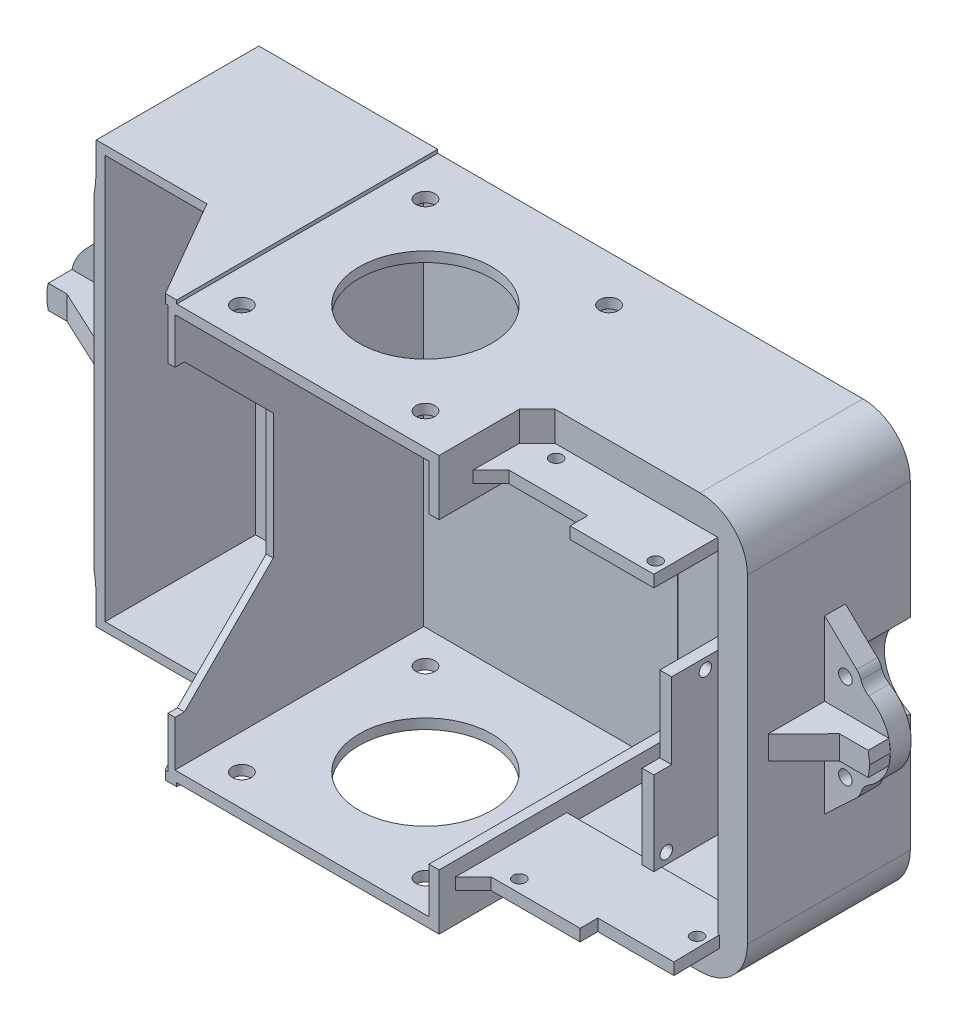
SolidWorks part; units mm, degrees
ref_plane "Front Plane" through (0, 0, 0) normal (0, 0, 1) x (1, 0, 0)
ref_plane "Top Plane" through (0, 0, 0) normal (0, 1, 0) x (1, 0, 0)
ref_plane "Right Plane" through (0, 0, 0) normal (1, 0, 0) x (0, 0, -1)
sketch "Sketch1" plane through (0, 0, 0) normal (0, 0, 1) x (1, 0, 0)
  line L0 (-51.35, -35.6) -> (-51.35, 35.6)
  line L13 (-51.35, 35.6) -> (-21.15, 35.6)
  line L14 (-21.15, -35.6) -> (-21.15, -35)
  line L15 (-51.35, -35.6) -> (-21.15, -35.6)
  line L20 (11, 35) -> (-11, 35) construction
  line L22 (-11, -35) -> (-21.15, -35)
  line L23 (-11, -35) -> (11, -35)
  line L24 (21.15, 33) -> (21.15, 9.5) construction
  line L25 (-21.15, 35) -> (-21.15, 35.6)
  line L29 (23.15, -35) -> (11, -35)
  line L30 (-21.15, 35) -> (23.15, 35)
  line L31 (23.15, 35) -> (23.15, -35)
  line L35 (-21.15, -9.5) -> (-21.15, -33) construction
  line L36 (-23.15, 33.6) -> (-49.35, 33.6) construction
  line L37 (-23.15, -33.6) -> (-49.35, -33.6) construction
  line L38 (-49.35, 33.6) -> (-49.35, -33.6) construction
  point P31 (-23.15, 35)
  dimension "D1" = 2
  dimension "D2" = 2
  dimension "D3" = 2
  dimension "D4" = 2
extrude "Boss-Extrude1" add sketch "Sketch1" along normal up to surface (2.0675 mm away) from offset 2.5
sketch "Sketch2" plane through (0, 0, 4.5675) normal (0, 0, 1) x (1, 0, 0)
  line L0 (-51.35, 35.6) -> (-49.85, 35.6) construction
  line L1 (-21.15, 35.6) -> (-51.35, 35.6) construction
  line L2 (-49.85, 35.6) -> (-49.85, 34.1) construction
  line L3 (-21.15, -35.6) -> (-22.65, -35.6) construction
  line L4 (-51.35, -35.6) -> (-21.15, -35.6) construction
  line L5 (-22.65, -35.6) -> (-22.65, -34.1) construction
  line L7 (-49.85, 34.1) -> (-22.65, 34.1)
  line L8 (-49.85, 34.1) -> (-49.85, -34.1)
  line L9 (-49.85, -34.1) -> (-22.65, -34.1)
  line L10 (-22.65, 34.1) -> (-22.65, -34.1)
  line L11 (-51.35, 35.6) -> (-21.15, 35.6)
  line L12 (-51.35, 35.6) -> (-51.35, -35.6)
  line L13 (-51.35, -35.6) -> (-21.15, -35.6)
  line L14 (-21.15, 35.6) -> (-21.15, -35.6)
  dimension "D1" = 1.5
  dimension "D2" = 1.5
  dimension "D3" = 1.5
  dimension "D4" = 1.5
extrude "Boss-Extrude2" add sketch "Sketch2" along normal blind 25.4
sketch "Sketch3" plane through (0, 0, 4.5675) normal (0, 0, 1) x (1, 0, 0)
  line L0 (-21.15, 33) -> (-21.15, 35)
  line L1 (23.15, -35) -> (-21.15, -35)
  line L2 (23.15, -35) -> (23.15, 35)
  line L3 (23.15, 35) -> (-21.15, 35)
  line L4 (-21.15, -35) -> (-21.15, -33)
  line L5 (21.15, -33) -> (-21.15, -33)
  line L6 (21.15, -33) -> (21.15, 33)
  line L7 (21.15, 33) -> (-21.15, 33)
  line M9 (-21.15, 35) -> (-21.15, -35)
  line M10 (-21.15, -35) -> (23.15, -35)
  line M11 (23.15, -35) -> (23.15, 35)
  line M12 (23.15, 35) -> (-21.15, 35)
extrude "Boss-Extrude3" add sketch "Sketch3" along normal blind 42 contours L7 L6 L5 M9 M10 M11 M12
sketch "Sketch4" plane through (0, 0, 29.9675) normal (0, 0, 1) x (1, 0, 0)
  line L0 (-21.15, 35.6) -> (-51.35, 35.6) construction
  line L1 (-21.15, -35.6) -> (-22.65, -35.6)
  line L2 (-21.15, -35.6) -> (-21.15, -25.6)
  line L3 (-21.15, 35.6) -> (-22.65, 35.6)
  line L5 (-22.65, -35.6) -> (-22.65, -25.6) construction
  line L6 (-22.65, 35.6) -> (-22.65, 25.6) construction
  line L7 (-22.65, -34.1) -> (-22.65, 34.1) construction
  line L8 (-22.65, -25.6) -> (-22.65, -35.6)
  line L9 (-22.65, -25.6) -> (-21.15, -25.6)
  line L10 (-22.65, 25.6) -> (-21.15, 25.6)
  line L11 (-22.65, 25.6) -> (-22.65, 35.6)
  line L12 (-21.15, 25.6) -> (-21.15, 35.6)
  dimension "D1" = 10
  dimension "D2" = 10
extrude "Boss-Extrude5" add sketch "Sketch4" along normal up to surface (16.6 mm away) up to face at (0.5, 0, 46.5675)
sketch "Sketch5" plane through (0, 0, 46.5675) normal (0, 0, 1) x (1, 0, 0)
  line L0 (-21.15, -25.6) -> (21.15, -25.6) construction
  line L1 (21.15, -33) -> (21.15, 33) construction
  line L2 (-21.15, 25.6) -> (21.15, 25.6) construction
  line L3 (23.15, -35) -> (23.15, 35) construction
  line L4 (21.15, 25.6) -> (23.15, 25.6)
  line L5 (21.15, 25.6) -> (21.15, -25.6)
  line L6 (21.15, -25.6) -> (23.15, -25.6)
  line L7 (23.15, 25.6) -> (23.15, -25.6)
extrude "Cut-Extrude1" cut sketch "Sketch5" against normal offset from surface (37 mm away) 5 up to face at (0, 0, 4.5675)
sketch "Sketch6" plane through (0, 0, 2.5) normal (0, 0, -1) x (-1, 0, 0)
  line L0 (0, 0) -> (-53.65, 0) construction
  line L1 (-53.65, -45.2197) -> (-53.65, 45.2197) construction
  line L2 (-23.15, -35) -> (-58.65, -35) construction
  line L4 (-23.15, 35) -> (-58.65, 35) construction
  line L7 (-23.15, 35) -> (-58.65, 35)
  line L8 (-23.15, 35) -> (-23.15, -35)
  line L9 (-23.15, -35) -> (-58.65, -35)
  line L10 (-58.65, 35) -> (-58.65, -35)
  line L12 (-53.65, 13.5) -> (-53.65, -13.5) construction
  point P3 (-53.4455, -18.8267)
  point P8 (-53.65, 0)
  dimension "D1" = 5
extrude "Boss-Extrude6" add sketch "Sketch6" against normal blind 2
sketch "Sketch7" plane through (0, 0, 4.5) normal (0, 0, 1) x (1, 0, 0)
  line L0 (23.15, -35) -> (23.15, -25.6) construction
  line L3 (53.65, -30) -> (23.15, -30)
  line L9 (23.15, 25.6) -> (23.15, 35) construction
  line L17 (53.65, -30) -> (53.65, 30)
  line L18 (58.65, -35) -> (58.65, 35)
  line L19 (23.15, -35) -> (58.65, -35)
  line L20 (23.15, 35) -> (58.65, 35)
  line L22 (23.15, 35) -> (23.15, 30)
  line L23 (23.15, -30) -> (23.15, -35)
  line L24 (53.65, 13.5) -> (53.65, -13.5) construction
  line L25 (23.15, 30) -> (53.65, 30)
  dimension "D1" = 5
  dimension "D2" = 5
  dimension "D3" = 5
extrude "Boss-Extrude7" add sketch "Sketch7" along normal up to surface (25.5 mm away)
sketch "Sketch9" plane through (0, 0, 46.5675) normal (0, 0, 1) x (1, 0, 0)
  line L1 (-21.15, -33) -> (21.15, -33)
  line L2 (-21.15, -33) -> (-21.15, 33)
  line L3 (-21.15, 33) -> (21.15, 33)
  line L4 (21.15, -33) -> (21.15, 33)
  line L12 (21.45, 33.3) -> (-21.45, 33.3)
  line L13 (-21.45, 33.3) -> (-21.45, -33.3)
  line L14 (-21.45, -33.3) -> (21.45, -33.3)
  line L15 (21.45, -33.3) -> (21.45, 33.3)
  line L16 (21.45, 33.3) -> (-21.45, 33.3)
  line L17 (-21.45, 33.3) -> (-21.45, -33.3)
  line L18 (-21.45, -33.3) -> (21.45, -33.3)
  line L19 (21.45, -33.3) -> (21.45, 33.3)
  dimension "D1" = 0.3
extrude "Cut-Extrude2" cut sketch "Sketch9" against normal up to surface (42 mm away) up to face at (0, 0, 4.5675)
sketch "Sketch10" plane through (0, 30, 0) normal (0, -1, 0) x (1, 0, 0)
  line L0 (53.65, 40.8) -> (53.65, 15)
  line L1 (53.65, 15) -> (23.15, 15)
  line L2 (23.15, 30) -> (23.15, 4.5) construction
  line L3 (23.15, 15) -> (23.15, 37.8)
  line L4 (23.15, 37.8) -> (39.5, 37.8)
  line L5 (39.5, 37.8) -> (39.5, 40.8)
  line L6 (39.5, 40.8) -> (53.65, 40.8)
  line L7 (53.65, 30) -> (23.15, 30) construction
  line L8 (36.5, 40.8) -> (36.5, 43.2) construction
  line L9 (26.65, 40.8) -> (36.5, 40.8) construction
  dimension "D1" = 15
  dimension "D2" = 3
  dimension "D3" = 3
extrude "Boss-Extrude8" add sketch "Sketch10" along normal blind 2
sketch "Sketch11" plane through (0, -30, 0) normal (0, 1, 0) x (1, 0, 0)
  line L1 (23.15, -15) -> (53.65, -15)
  line L2 (53.65, -30) -> (53.65, -4.5) construction
  line L3 (53.65, -15) -> (54.0399, -37.8)
  line L4 (54.0399, -40.8) -> (54.0399, -30) construction
  line L5 (54.0399, -37.8) -> (41.1899, -37.8)
  line L6 (41.1899, -37.8) -> (41.1899, -40.8)
  line L7 (41.1899, -40.8) -> (27.0399, -40.8)
  line L8 (44.1899, -40.8) -> (44.1899, -43.2) construction
  line L9 (54.0399, -40.8) -> (44.1899, -40.8) construction
  line L10 (23.15, -30) -> (53.65, -30) construction
  line L11 (23.15, -30) -> (23.15, -4.5) construction
  line L12 (23.15, -15) -> (23.15, -40.8)
  line L13 (23.15, -40.8) -> (27.0399, -40.8)
  dimension "D1" = 3
  dimension "D2" = 3
  dimension "D3" = 15
extrude "Boss-Extrude9" add sketch "Sketch11" along normal blind 2
sketch "Sketch12" plane through (53.65, 0, 0) normal (-1, 0, 0) x (0, 0, 1)
  line L0 (40.8, -13.5) -> (25, -13.5)
  line L1 (25, -13.5) -> (25, 13.5)
  line L2 (25, 13.5) -> (37.8, 13.5)
  line L4 (37.8, 13.5) -> (37.8, 0.65)
  line L5 (37.8, 0.65) -> (40.8, 0.65)
  line L6 (40.8, 0.65) -> (40.8, -13.5)
  line L7 (40.8, 3.65) -> (40.8, -13.5) construction
  line L8 (40.8, 3.65) -> (43.2, 3.65) construction
  line L9 (40.8, 13.5) -> (40.8, 3.65) construction
  line L10 (30, -28) -> (30, 28) construction
  line L11 (40.8, 13.5) -> (30, 13.5) construction
  dimension "D1" = 3
  dimension "D2" = 3
  dimension "D3" = 5
extrude "Boss-Extrude10" add sketch "Sketch12" along normal blind 2
sketch "Sketch13" plane through (0, -30, 0) normal (0, -1, 0) x (-1, 0, 0)
  circle A0 centre (-28.8399, -38.7) radius 1.05
  circle A1 centre (-52.2399, -32.1) radius 1.05
  dimension "D1" = 2.1
extrude "Cut-Extrude3" cut sketch "Sketch13" against normal up to next
sketch "Sketch14" plane through (53.65, 0, 0) normal (1, 0, 0) x (0, 0, -1)
  circle A0 centre (-32.1, 11.7) radius 1.05
  circle A1 centre (-38.7, -11.7) radius 1.05
  dimension "D1" = 2.1
extrude "Cut-Extrude4" cut sketch "Sketch14" against normal up to next
sketch "Sketch15" plane through (0, 30, 0) normal (0, 1, 0) x (1, 0, 0)
  circle A0 centre (28.45, -32.1) radius 1.05
  circle A1 centre (51.85, -38.7) radius 1.05
  dimension "D1" = 2.1
extrude "Cut-Extrude5" cut sketch "Sketch15" against normal up to next
sketch "Sketch16" plane through (0, 0, 0) normal (0, 0, 1) x (1, 0, 0)
  line L1 (-51.35, 35.6) -> (-51.35, -35.6) construction
  line L3 (-58.0347, 14.5306) -> (-66.0201, 5.8279)
  line L4 (-58.0347, -14.5306) -> (-66.0201, -5.8279)
  line L10 (-51.35, 31.7086) -> (-51.35, 0) construction
  line L11 (-51.35, 0) -> (-51.35, -31.7086) construction
  line L12 (0, 0) -> (-79.5, 0) construction
  line L13 (-51.35, -31.7086) -> (-51.35, 31.7086)
  arc A1 (-66.0201, 5.8279) -> (-66.0201, -5.8279) centre (-59.6687, 0) ccw
  arc A2 (-51.35, 31.7086) -> (-58.0347, 14.5306) centre (-76.75, 31.7032) cw
  arc A3 (-51.35, -31.7086) -> (-58.0347, -14.5306) centre (-76.75, -31.7032) ccw
  arc A4 (-63.6443, 6.5007) -> (-63.6443, -6.5007) centre (-59.6687, 0) ccw construction
  dimension "D3" = 25.4
  dimension "D4" = 25.4
  dimension "D2" = 1
extrude "Boss-Extrude11" add sketch "Sketch16" along normal blind 3.9 from surface at 13.462
sketch "Sketch17" plane through (0, 0, 13.462) normal (0, 0, -1) x (-1, 0, 0)
  circle A0 centre (59.6687, 7.366) radius 1.25
  circle A1 centre (59.6687, -7.366) radius 1.25
  dimension "D1" = 2.5
extrude "Cut-Extrude6" cut sketch "Sketch17" against normal up to next
chamfer "Chamfer1" distance 10 angle 45 1 edges at (38.4, -28, 15)
chamfer "Chamfer2" distance 10 angle 45 1 edges at (38.4, 28, 15)
chamfer "Chamfer3" distance 3 angle 45 1 edges at (51.65, 0, 25)
fillet "Fillet1" radius 8 1 edges at (58.65, -35, 16.25)
fillet "Fillet2" radius 8 1 edges at (58.65, 35, 16.25)
chamfer "Chamfer4" distance 3 angle 45 1 edges at (23.15, -32.5, 30)
chamfer "Chamfer5" distance 3 angle 45 1 edges at (23.15, 32.5, 30)
chamfer "Chamfer6" distance 3 angle 45 1 edges at (23.15, -29, 40.8)
chamfer "Chamfer7" distance 3 angle 45 1 edges at (23.15, 29, 37.8)
sketch "Sketch18" plane through (0, -35, 0) normal (0, -1, 0) x (1, 0, 0)
  line L0 (0, 25.7175) -> (0, 41.2175) construction
  line L1 (0, 41.2175) -> (-15.5, 41.2175) construction
  line L2 (-15.5, 41.2175) -> (-15.5, 10.2175) construction
  line L3 (-15.5, 10.2175) -> (15.5, 10.2175) construction
  line L4 (15.5, 10.2175) -> (15.5, 41.2175) construction
  circle A0 centre (0, 25.7175) radius 11.2
  circle A1 centre (-15.5, 41.2175) radius 1.6
  circle A2 centre (15.5, 41.2175) radius 1.6
  circle A3 centre (15.5, 10.2175) radius 1.6
  circle A4 centre (-15.5, 10.2175) radius 1.6
  dimension "D1" = 22.4
  dimension "D4" = 3.2
  dimension "D2" = 15.5
  dimension "D3" = 15.5
  dimension "D7" = 31
  dimension "D8" = 31
  dimension "D5" = 2
  dimension "D6" = 2
extrude "Cut-Extrude7" cut sketch "Sketch18" against normal through all
chamfer "Chamfer8" distance 10 angle 60 1 edges at (-22.65, -34.85, 29.9675)
chamfer "Chamfer9" distance 10 angle 60 1 edges at (-22.65, 34.85, 29.9675)
chamfer "Chamfer10" distance 5 angle 70 1 edges
sketch "Sketch19" plane through (0, 0, 17.362) normal (0, 0, 1) x (1, 0, 0)
  line L0 (-56.35, 0) -> (-68.2887, 0) construction
  line L1 (-56.35, -16.5705) -> (-56.35, 16.5705) construction
  line L2 (-52.8423, 2) -> (-52.8423, -2)
  line L3 (-52.8423, 2) -> (-68.0535, 2)
  line L4 (-52.8423, -2) -> (-68.0535, -2)
  line L5 (-56.35, 0) -> (-56.35, 2) construction
  line L6 (-56.35, 0) -> (-56.35, -2) construction
  arc A0 (-66.0201, 5.8279) -> (-66.0201, -5.8279) centre (-59.6687, 0) ccw construction
  arc A1 (-68.0535, 2) -> (-68.0535, -2) centre (-59.6687, 0) ccw
  point P10 (-52.8423, 0)
  dimension "D1" = 4
extrude "Boss-Extrude13" add sketch "Sketch19" along normal blind 4
chamfer "Chamfer11" distance 10 angle 25 1 edges at (-54.8941, 0, 21.362)
chamfer "Chamfer12" distance 15 angle 45 1 edges at (-22.05, -25.6, 29.9675)
chamfer "Chamfer13" distance 15 angle 45 1 edges at (-22.05, 25.6, 29.9675)
sketch "Sketch20" plane through (0, 0, 2.5) normal (0, 0, -1) x (-1, 0, 0)
  circle A1 centre (-62.15, 0) radius 7.87
extrude "Cut-Extrude8" cut sketch "Sketch20" against normal up to surface (10.962 mm away)
sketch "Sketch21" plane through (0, 0, 13.462) normal (0, 0, -1) x (-1, 0, 0)
  line L0 (-58.65, 27) -> (-58.65, 14.5) construction
  line L1 (-58.65, 27) -> (-58.65, 7.0489) construction
  line L2 (-58.65, -27) -> (-58.65, -14.5) construction
  line L3 (-58.65, -7.0489) -> (-58.65, -27) construction
  line L4 (-58.65, -14.5) -> (-64.0655, -9.4)
  line L5 (-58.65, 14.5) -> (-64.054, 9.3729)
  line L6 (-58.65, 14.5) -> (-58.65, -14.5)
  circle A0 centre (-62.15, 7.366) radius 1.143
  circle A1 centre (-62.15, -7.366) radius 1.143
  arc A2 (-64.054, 9.3729) -> (-64.7911, 8.1891) centre (-62.15, 7.366) ccw
  arc A3 (-64.8219, -8.1829) -> (-64.0655, -9.4) centre (-62.15, -7.366) ccw
  arc A6 (-66.1001, 6.5162) -> (-66.1256, -6.5007) centre (-62.15, 0) ccw
  arc A7 (-66.1256, -6.5007) -> (-64.8219, -8.1829) centre (-67.6908, -9.06) cw
  arc A8 (-66.1001, 6.5162) -> (-64.7911, 8.1891) centre (-67.6553, 9.0817) ccw
  dimension "D1" = 3
  dimension "D3" = 2.286
  dimension "D4" = 2.286
  dimension "D5" = 7.62
  dimension "D6" = 2.7664
  dimension "D7" = 2.794
  dimension "D2" = 12.5
extrude "Boss-Extrude14" add sketch "Sketch21" against normal blind 3.5
sketch "Sketch22" plane through (0, 0, 16.962) normal (0, 0, 1) x (1, 0, 0)
  line L0 (58.65, 0) -> (69.77, 0.0149) construction
  line L1 (58.65, -14.5) -> (58.65, 14.5) construction
  line L2 (58.6527, -2) -> (69.5068, -1.9854)
  line L3 (58.6473, 2) -> (69.5068, 2.0146)
  line L4 (69.77, 0.0149) -> (69.5068, -1.9854)
  line L5 (69.77, 0.0149) -> (69.5068, 2.0146)
  line L6 (58.6527, -2) -> (58.6473, 2)
  line L7 (58.6473, 2) -> (69.7673, 2.0149) construction
  line L8 (58.6527, -2) -> (69.7727, -1.9851) construction
  arc A0 (66.1256, -6.5007) -> (66.1001, 6.5162) centre (62.15, 0) ccw construction
  dimension "D1" = 2
  dimension "D2" = 2
extrude "Boss-Extrude15" add sketch "Sketch22" along normal blind 3.5
chamfer "Chamfer14" distance 6 angle 45 1 edges at (58.65, 1, 20.462)
sketch "Sketch23" plane through (0, 0, 9.5675) normal (0, 0, 1) x (1, 0, 0)
  line L1 (21.45, 25.6) -> (23.15, 25.6)
  line L2 (21.45, 25.6) -> (21.45, -25.6)
  line L3 (21.45, -25.6) -> (23.15, -25.6)
  line L4 (23.15, 25.6) -> (23.15, -25.6)
extrude "Cut-Extrude9" cut sketch "Sketch23" against normal up to surface (5.0675 mm away) up to face at (38.4, 0, 4.5)
